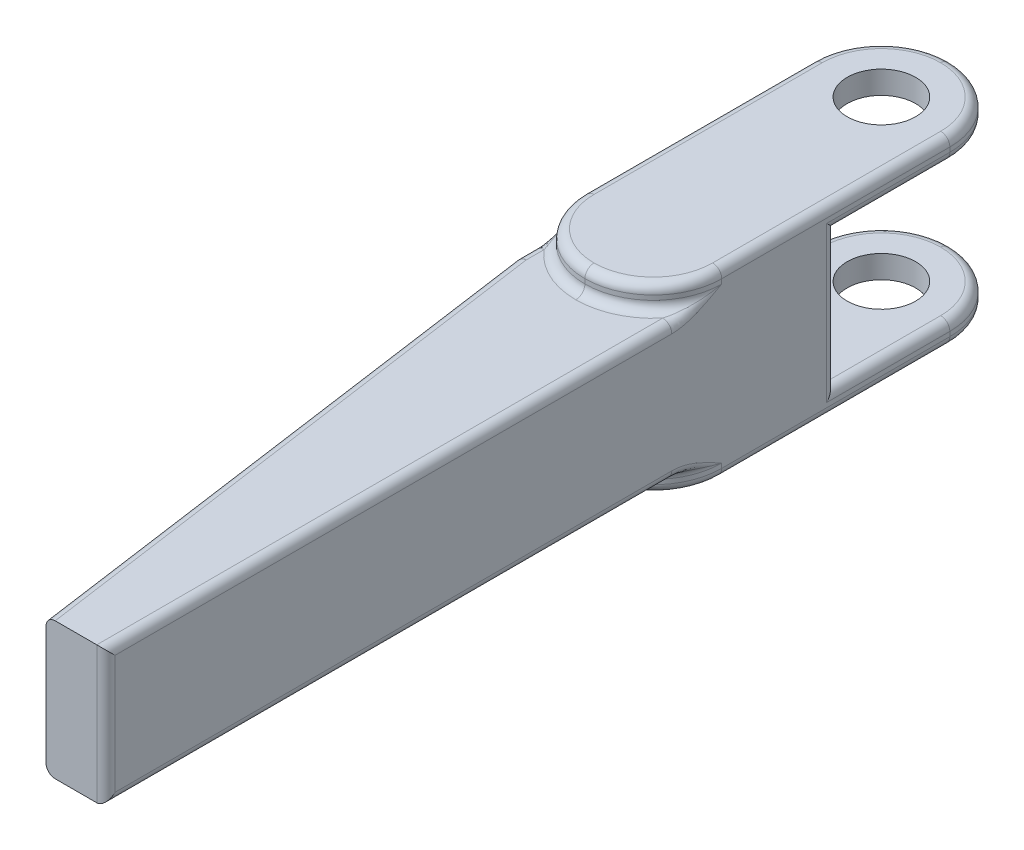
SolidWorks part; units mm, degrees
ref_plane "Front Plane" through (0, 0, 0) normal (0, 0, 1) x (1, 0, 0)
ref_plane "Top Plane" through (0, 0, 0) normal (0, 1, 0) x (1, 0, 0)
ref_plane "Right Plane" through (0, 0, 0) normal (1, 0, 0) x (0, 0, -1)
sketch "Esquisse1" plane through (0, 0, 0) normal (0, 0, 1) x (1, 0, 0)
  line L1 (-15, -15) -> (15, -15)
  line L2 (-15, -15) -> (-15, 15)
  line L3 (-15, 15) -> (15, 15)
  line L4 (15, -15) -> (15, 15)
  line L5 (-15, -15) -> (15, 15) construction
  line L6 (-15, 15) -> (15, -15) construction
  point P0 (0, 0)
  dimension "D1" = 30
  dimension "D2" = 30
extrude "Boss.-Extru.1" add sketch "Esquisse1" along normal blind 160
sketch "Esquisse2" plane through (0, 0, 0) normal (0, 0, -1) x (-1, 0, 0)
  line L0 (-15, 15) -> (15, 15) construction
  line L1 (15, -20) -> (-15, -20)
  line L2 (15, -20) -> (15, 20)
  line L3 (15, 20) -> (-15, 20)
  line L4 (-15, -20) -> (-15, 20)
  line L5 (15, -20) -> (-15, 20) construction
  line L6 (15, 20) -> (-15, -20) construction
  point P0 (0, 0)
  line M6 (-15, -15) -> (15, -15)
  line M8 (15, 15) -> (-15, 15)
  dimension "D1" = 40
extrude "Boss.-Extru.2" add sketch "Esquisse2" against normal mid plane 80 contours L4 L2 L3 M8 | L4 L1 L2 M6 region at (0, -17.5, 0) region at (0, 17.5, 0)
fillet "Congé1" radius 15 8 edges at (15, -17.5, 40) (-15, -17.5, 40) (-15, 17.5, 40) (15, 17.5, 40) (15, -17.5, -40) (-15, -17.5, -40) (-15, 17.5, -40) (15, 17.5, -40)
sketch "Esquisse3" plane through (0, -20, 0) normal (0, -1, 0) x (1, 0, 0)
  circle A0 centre (0, -25) radius 7.5
  dimension "D1" = 15
extrude "Enlèv. mat.-Extru.1" cut sketch "Esquisse3" against normal through all
chamfer "Chanfrein1" distance 120 angle 8 1 edges at (-15, 0, 160) first distance on face at (-15, 0, 26.6667)
fillet "Congé2" radius 2 34 edges at (10.6066, -15, -35.6066) (-10.6066, -15, -35.6066) (-15, -15, -12.5) (-15, 0, 0) (-15, 15, -12.5) (-10.6066, 15, -35.6066) (10.6066, 15, -35.6066) (15, 15, -12.5) (15, 0, 0) (15, -15, -12.5) (-10.6066, 20, 35.6066) (10.6066, 20, 35.6066) (15, 20, 0) (10.6066, 20, -35.6066) (-10.6066, 20, -35.6066) (-15, 20, 0) (10.6066, -20, 35.6066) (-10.6066, -20, 35.6066) (-15, -20, 0) (-10.6066, -20, -35.6066) (10.6066, -20, -35.6066) (15, -20, 0) (15, 0, 160) (15, 15, 92.5) (10.6066, 15, 35.6066) (-10.6066, 15, 35.6066) (-15, 15, 32.5) (-15, 0, 40) (-15, -15, 32.5) (-10.6066, -15, 35.6066) (10.6066, -15, 35.6066) (15, -15, 92.5) (-6.5675, -15, 100) (-6.5675, 15, 100)
